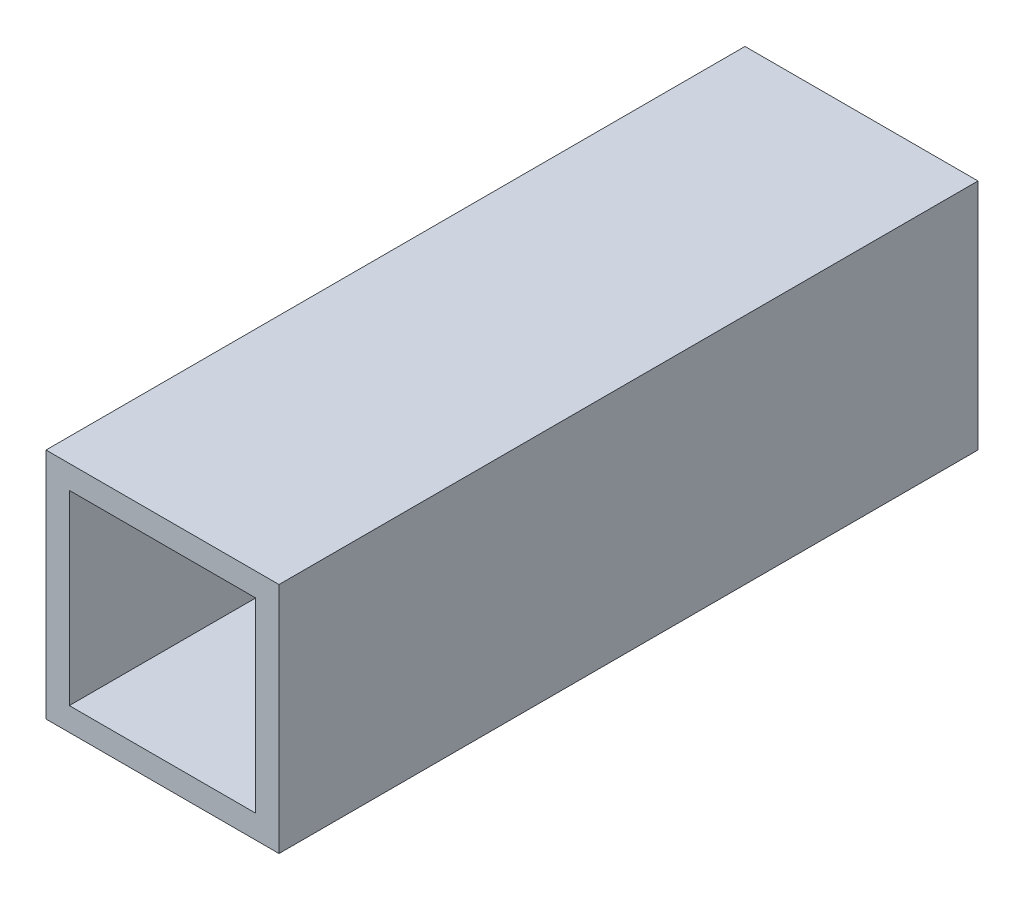
SolidWorks part; units mm, degrees
ref_plane "Front Plane" through (0, 0, 0) normal (0, 0, 1) x (1, 0, 0)
ref_plane "Top Plane" through (0, 0, 0) normal (0, 1, 0) x (1, 0, 0)
ref_plane "Right Plane" through (0, 0, 0) normal (1, 0, 0) x (0, 0, -1)
sketch "Sketch1" plane through (0, 0, 0) normal (0, 0, 1) x (1, 0, 0)
  line L0 (-20, 20) -> (-20, -20)
  line L1 (-25, 25) -> (25, 25)
  line L2 (-25, 25) -> (-25, -25)
  line L3 (-25, -25) -> (25, -25)
  line L4 (25, 25) -> (25, -25)
  line L5 (-20, -20) -> (20, -20)
  line L6 (20, 20) -> (20, -20)
  line L7 (-20, 20) -> (20, 20)
  dimension "tube_width" = 50
  dimension "D1" = 50
  dimension "D3" = 25
  dimension "D4" = 25
  dimension "tube_thickness" = 5
extrude "Boss-Extrude1" add sketch "Sketch1" along normal blind 150
sketch "Sketch2" plane through (0, 25, 0) normal (0, 1, 0) x (1, 0, 0)
  text T0 "<r180>z</r>" font "Century Gothic" height 40
equation "\"D1@Sketch1\"= \"tube_width@Sketch1\""
equation "\"D3@Sketch1\"=\"tube_width@Sketch1\"/2"
equation "\"D4@Sketch1\"=\"tube_width@Sketch1\"/2"
